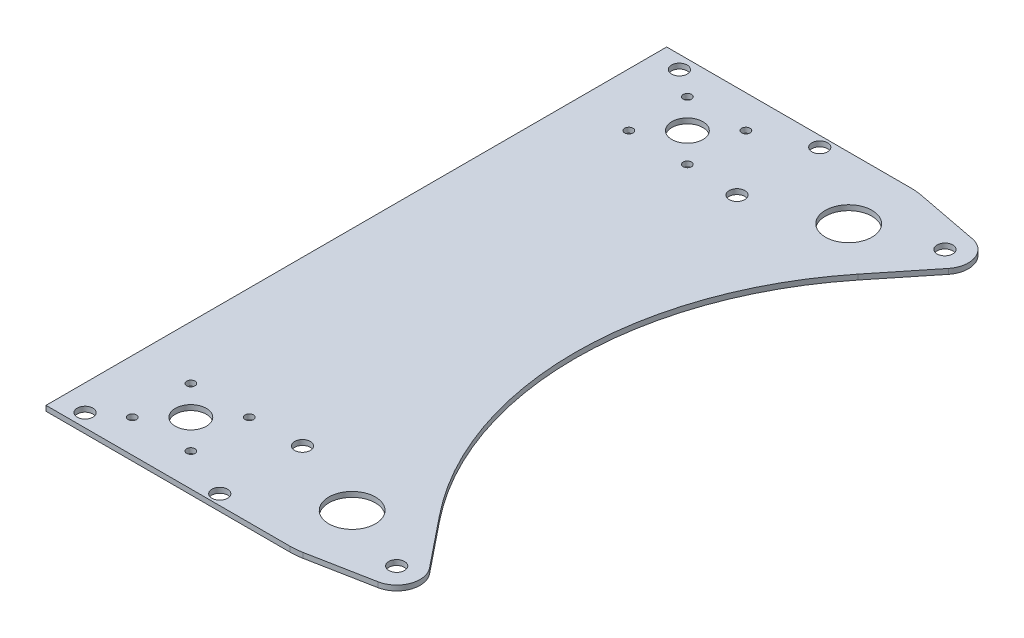
SolidWorks part; units mm, degrees
material "6061-T6 (SS)"
ref_plane "Front Plane" through (0, 0, 0) normal (0, 0, 1) x (1, 0, 0)
ref_plane "Top Plane" through (0, 0, 0) normal (0, 1, 0) x (1, 0, 0)
ref_plane "Right Plane" through (0, 0, 0) normal (1, 0, 0) x (0, 0, -1)
sketch "Sketch1" plane through (0, 0, 0) normal (0, 1, 0) x (1, 0, 0)
  line L1 (120.65, -190.5) -> (-120.65, -190.5)
  line L2 (120.65, -190.5) -> (120.65, 190.5)
  line L3 (120.65, 190.5) -> (-120.65, 190.5)
  line L4 (-120.65, -190.5) -> (-120.65, 190.5)
  line L5 (120.65, -190.5) -> (-120.65, 190.5) construction
  line L6 (120.65, 190.5) -> (-120.65, -190.5) construction
  point P0 (0, 0)
  dimension "D1" = 241.3
  dimension "D2" = 381
extrude "Boss-Extrude1" add sketch "Sketch1" along normal blind 3.175
sketch "Sketch6" plane through (0, 3.175, 0) normal (0, 1, 0) x (1, 0, 0)
  line L1 (-69.85, 152.4) -> (0, 0) construction
  line L2 (0, 0) -> (-69.85, -152.4) construction
  line L5 (-120.65, 190.5) -> (-120.65, -190.5) construction
  circle A0 centre (-69.85, -152.4) radius 38.1 construction
  circle A1 centre (-69.85, 152.4) radius 38.1 construction
  circle A2 centre (29.1592, -152.4) radius 38.1 construction
  circle A3 centre (29.1592, 152.4) radius 38.1 construction
  dimension "D1" = 76.2
  dimension "D5" = 228.6
  dimension "D3" = 99.0092
  dimension "D4" = 50.8
sketch "Sketch7" plane through (0, 3.175, 0) normal (0, 1, 0) x (1, 0, 0)
  circle A0 centre (29.1592, -152.4) radius 14.2875
  circle A1 centre (29.1592, 152.4) radius 14.2875
  circle A2 centre (-69.85, 152.4) radius 9.525
  circle A3 centre (-69.85, -152.4) radius 9.525
  circle A4 centre (-87.8105, 170.3605) radius 2.5527
  circle A5 centre (-69.85, 152.4) radius 25.4 construction
  circle A6 centre (-51.8895, 170.3605) radius 2.5527
  circle A7 centre (-51.8895, 134.4395) radius 2.5527
  circle A8 centre (-87.8105, 134.4395) radius 2.5527
  circle A9 centre (-69.85, -152.4) radius 25.4 construction
  circle A10 centre (-87.8105, -134.4395) radius 2.5527
  circle A11 centre (-51.8895, -134.4395) radius 2.5527
  circle A12 centre (-51.8895, -170.3605) radius 2.5527
  circle A13 centre (-87.8105, -170.3605) radius 2.5527
  point P24 (-69.85, 152.4)
  point P34 (-69.85, -152.4)
  dimension "D1" = 28.575
  dimension "D2" = 19.05
  dimension "D3" = 5.1054
  dimension "D5" = 50.8
  dimension "D4" = 4
  dimension "D6" = 4
extrude "Axle Holes" cut sketch "Sketch7" against normal through all
sketch "Sketch10" plane through (0, 3.175, 0) normal (0, 1, 0) x (1, 0, 0)
  line L0 (0, 0) -> (57.9248, 0) construction
  circle A0 centre (-104.775, -182.3949) radius 4.826
  circle A1 centre (-20.3454, -184.15) radius 4.826
  circle A2 centre (-20.3454, -133.35) radius 2.5527 construction
  circle A3 centre (-20.3454, -133.35) radius 4.826
  circle A4 centre (72.373, -168.275) radius 4.826
  circle A10 centre (-104.775, -182.3949) radius 2.5527 construction
  circle A11 centre (-20.3454, -184.15) radius 2.5527 construction
  circle A12 centre (72.373, -168.275) radius 2.5527 construction
  circle A13 centre (-20.3454, -133.35) radius 2.5527 construction
  circle A14 centre (-104.775, -182.3949) radius 2.5527 construction
  circle A15 centre (-20.3454, -184.15) radius 2.5527 construction
  circle A16 centre (72.373, -168.275) radius 2.5527 construction
  circle A17 centre (72.373, 168.275) radius 4.826
  circle A18 centre (-20.3454, 184.15) radius 4.826
  circle A19 centre (-20.3454, 133.35) radius 4.826
  circle A20 centre (-104.775, 182.3949) radius 4.826
  dimension "D1" = 9.652
extrude "Cut-Extrude5" cut sketch "Sketch10" against normal through all
sketch "Sketch8" plane through (0, 3.175, 0) normal (0, 1, 0) x (1, 0, 0)
  line L0 (58.863, -128.5401) -> (83.5615, -159.2878)
  line L1 (36.3532, -189.8147) -> (75.0828, -182.3679)
  line L5 (0, 0) -> (-35.0112, 0) construction
  line L6 (58.863, 128.5401) -> (83.5615, 159.2878)
  line L7 (36.3532, 189.8147) -> (75.0828, 182.3679)
  circle A4 centre (29.1592, -152.4) radius 38.1 construction
  circle A5 centre (72.373, -168.275) radius 14.351 construction
  arc A7 (75.0828, -182.3679) -> (83.5615, -159.2878) centre (72.373, -168.275) ccw
  arc A8 (58.863, -128.5401) -> (58.863, 128.5401) centre (218.8853, 0) cw
  circle A9 centre (72.373, -168.275) radius 4.826 construction
  arc A10 (75.0828, 182.3679) -> (83.5615, 159.2878) centre (72.373, 168.275) cw
  arc A11 (36.3532, -189.8147) -> (29.1592, -190.5) centre (29.1592, -152.4) cw
  arc A12 (36.3532, 189.8147) -> (29.1592, 190.5) centre (29.1592, 152.4) ccw
  dimension "D2" = 9.525
  dimension "D1" = 76.2
extrude "Cut-Extrude4" cut sketch "Sketch8" against normal through all flip side to cut
